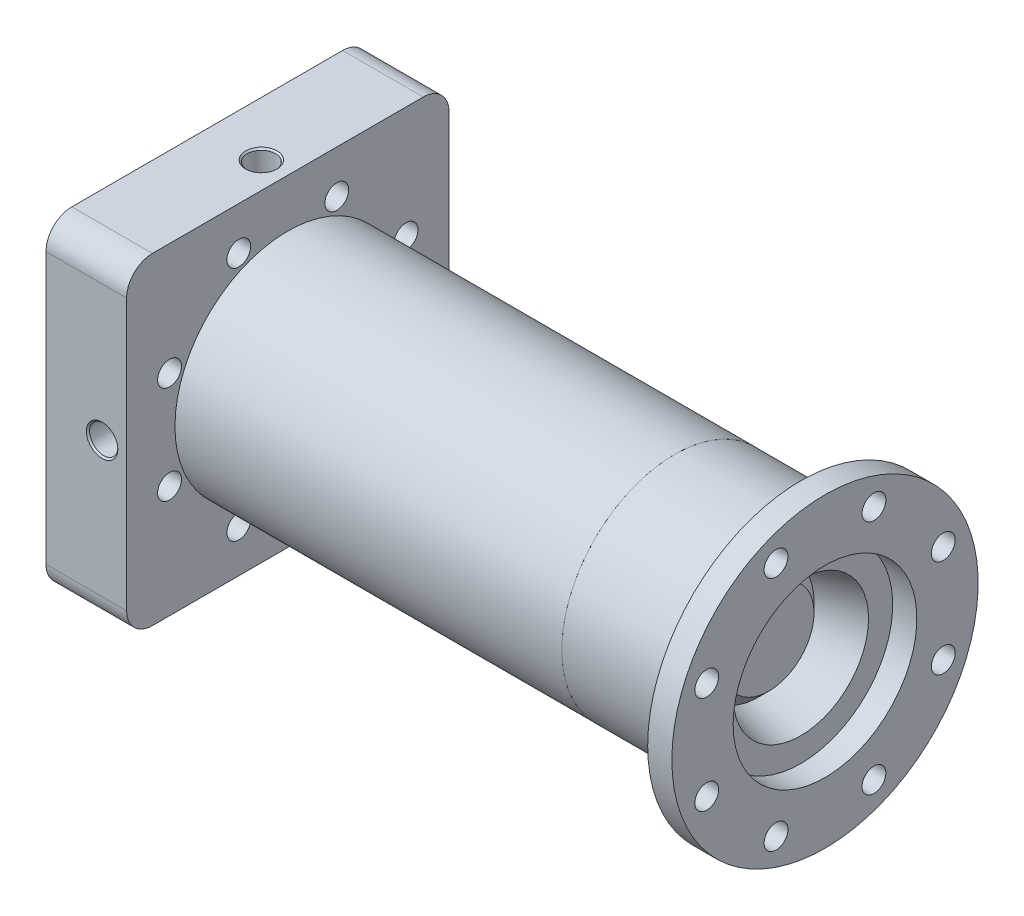
SolidWorks part; units mm, degrees
note: '?' marks a value the reader was unsure of.
other "TC"
other "Injector "
other "Volume "
other "Aft O Ring"
other "Forward O ring" parameters "D11"=9.6936, "D1"=8.9273, "D2"=33.6348, "D3"=26.5468, "D4"=23.315, "D5"=33.6348, "D6"=5.8865, "D7"=63.1196, "D8"=7.0953, "D9"=1.4619, "D10"=3.7307, "D12"=6.1926, "D13"=4.361, "D14"=3.81, "D15"=11.3511, "D16"=3.7343, "D17"=3.7343, "D18"=7.0449
ref_plane "Front Plane" through (0, 0, 0) normal (0, 0, 1) x (1, 0, 0)
ref_plane "Top Plane" through (0, 0, 0) normal (0, 1, 0) x (1, 0, 0)
ref_plane "Right Plane" through (0, 0, 0) normal (1, 0, 0) x (0, 0, -1)
sketch "Chamber Revolve" plane through (0, 0, 0) normal (0, 0, 1) x (1, 0, 0)
  line L1 (227.4697, 63.5) -> (227.4697, 26.67)
  line L4 (189.463, 17.801) -> (173.736, 33.528)
  line L5 (173.736, 33.528) -> (0, 33.528)
  line L10 (0, 33.528) -> (0, 42.164)
  line L11 (0, 63.5) -> (10.16, 63.5)
  line L12 (10.16, 63.5) -> (10.16, 47.244)
  line L13 (0, 0) -> (66.3921, 0) construction
  line L15 (191.9165, 17.1436) -> (227.4697, 26.67)
  line L16 (10.16, 47.244) -> (24.13, 47.244)
  line L17 (24.13, 47.244) -> (24.13, 63.5)
  line L18 (24.13, 63.5) -> (227.4697, 63.5)
  line L19 (190.5, 16.764) -> (191.9165, 17.1436) construction
  line L20 (190.5, 16.764) -> (189.463, 17.801) construction
  line L21 (0, 48.2346) -> (3.8608, 48.2346)
  line L22 (3.8608, 48.2346) -> (3.8608, 42.164)
  line L23 (3.8608, 42.164) -> (0, 42.164)
  line L24 (0, 48.2346) -> (0, 63.5)
  arc A0 (189.463, 17.801) -> (191.9165, 17.1436) centre (191.2591, 19.597) ccw
  dimension "D11" = 2.54
  dimension "D2" = 67.056
  dimension "D3" = 53.34
  dimension "D6" = 45
  dimension "D13" = 10.16
  dimension "D8" = 33.528
  dimension "D9" = 36.9697
  dimension "D7" = 13.716
  dimension "D15" = 13.97
  dimension "D5" = 190.5
  dimension "D4" = 15
  dimension "D18" = 6.0706
  dimension "D12" = 127
revolve "Revolve1" add sketch "Chamber Revolve" angle 360 about L13
fillet "Fillet1" radius 1.27 2 edges at (24.13, 0, 47.244) (10.16, 0, 47.244)
sketch "Sketch2" plane through (0, 0, 0) normal (-1, 0, 0) x (0, 0, 1)
  line L0 (0, 0) -> (-24.3004, 58.6664) construction
  line L1 (0, 0) -> (0, 56.6825) construction
  circle A0 centre (-21.7732, 52.565) radius 3.81
  circle A1 centre (0, 0) radius 63.5 construction
  dimension "D2" = 7.62
  dimension "D1" = 6.604
  dimension "D3" = 22.5
extrude "Cut-Extrude1" cut sketch "Sketch2" against normal up to next
pattern_circular "CirPattern1" count 8 over 360 about axis through (0, 0, 0) along (1, 0, 0) of "Cut-Extrude1"
sketch "Sketch4" plane through (0, 0, 0) normal (-1, 0, 0) x (0, 0, 1)
  circle A0 centre (0, 0) radius 63.5
  circle A1 centre (0, 0) radius 63.5 construction
extrude "Boss-Extrude1" add sketch "Sketch4" along normal blind 31.75 separate body
sketch "Sketch5" plane through (0, 0, 0) normal (1, 0, 0) x (0, 0, -1)
  circle A0 centre (21.7732, 52.565) radius 3.81 construction
  circle A1 centre (21.7732, 52.565) radius 3.81
sketch "Sketch11" plane through (-31.75, 0, 0) normal (-1, 0, 0) x (0, 0, 1)
  line L1 (-63.5, -63.5) -> (63.5, -63.5)
  line L2 (-63.5, -63.5) -> (-63.5, 63.5)
  line L3 (-63.5, 63.5) -> (63.5, 63.5)
  line L4 (63.5, -63.5) -> (63.5, 63.5)
  circle A0 centre (0, 0) radius 63.5 construction
  circle A1 centre (0, 0) radius 63.5
  point P6 (0, 63.5)
  point P9 (-63.5, 0)
  circle M18 centre (0, 0) radius 63.5
  dimension "D1" = 127
extrude "Boss-Extrude2" add sketch "Sketch11" against normal up to surface (31.75 mm away) contours L3 L2 L1 M18 | L1 L4 L3 M18 | L4 L3 M18 | L2 L1 M18
sketch "Sketch12" plane through (0, 0, 0) normal (1, 0, 0) x (0, 0, -1)
  circle A0 centre (0, 0) radius 24.13
  dimension "D1" = 48.26
extrude "Cut-Extrude4" cut sketch "Sketch12" against normal blind 16.51
sketch "Sketch13" plane through (0, 0, 63.5) normal (0, 0, 1) x (1, 0, 0)
  line L1 (0, 63.5) -> (0, -63.5) construction
  line L2 (76.835, 0) -> (-76.835, 0) construction
  circle A0 centre (-9.652, 0) radius 1.9685
  dimension "D1" = 3.937
  dimension "D2" = 9.652
extrude "Cut-Extrude5" cut sketch "Sketch13" against normal up to next and the other way through all
sketch "Sketch14" plane through (0, 0, 0) normal (1, 0, 0) x (0, 0, -1)
  line L0 (-63.5, 63.5) -> (63.5, 63.5) construction
  line L1 (-63.5, -63.5) -> (63.5, -63.5) construction
  line L2 (-12.7, 63.5) -> (-63.5, 63.5)
  line L3 (-63.5, 63.5) -> (-63.5, -63.5)
  line L4 (-63.5, -63.5) -> (-12.7, -63.5)
  arc A0 (-12.7, 63.5) -> (-12.7, -63.5) centre (0, 0) ccw
  circle A1 centre (0, 0) radius 63.5 construction
  dimension "D1" = 12.7
chamfer "Chamfer1" distance 4.572 angle 45 1 edges at (0, 0, -24.13)
sketch "Sketch18" plane through (0, 0, 63.5) normal (0, 0, 1) x (1, 0, 0)
  point P0 (-9.652, 0)
hole_wizard "7/16 (0.4375) Diameter Hole1" positions "Sketch18" profile "Sketch20" hole size "7/16" standard "ANSI Inch"
sketch "Sketch20" plane through (-9.652, 0, 63.5) normal (1, 0, 0) x (0, -1, 0)
  line L0 (0, 0) -> (0, 22.3885)
  line L1 (0, 22.3885) -> (5.5562, 19.05)
  line L2 (5.5562, 19.05) -> (5.5562, 0.635)
  line L3 (5.5562, 0.635) -> (6.1912, 0)
  line L5 (6.1912, 0) -> (0, 0)
  line L6 (-5.5562, 0.635) -> (-6.1912, 0) construction
  line L10 (0, 22.3885) -> (-5.5563, 19.05) construction
  line L11 (0, -6.35) -> (0, 107.95) construction
  dimension "Hole Dia." = 11.1125
  dimension "Hole Depth" = 19.05
  dimension "Near C'Sink Dia." = 12.3825
  dimension "Near C'Sink Angle" = 90
  dimension "Drill Angle" = 118
mirror "Mirror1" about plane through (0, 0, 0) normal (0, 0, 1) of "7/16 (0.4375) Diameter Hole1", "Cut-Extrude5"
sketch "Sketch21" plane through (0, 0, 0) normal (0, 1, 0) x (1, 0, 0)
  line L0 (0, 33.528) -> (173.736, 33.528)
  line L1 (0, 42.164) -> (0, -42.164) construction
  line L2 (0, 33.528) -> (0, -33.528) construction
  line L3 (173.736, -33.528) -> (173.736, 33.528) construction
  line L4 (173.736, 33.528) -> (189.463, 17.801)
  line L5 (189.463, -17.801) -> (189.463, 17.801) construction
  line L6 (189.463, 17.801) -> (189.463, 0)
  line L10 (0, 0) -> (0, 33.528)
  line L11 (0, 0) -> (189.463, 0)
  line L12 (189.463, 0) -> (214.4295, 0) construction
revolve "Revolve2" add sketch "Sketch21" angle 360 about L12
fillet "Fillet2" radius 0.889 2 edges at (3.8608, 0, 42.164) (3.8608, 0, 48.2346)
sketch "Sketch22" plane through (-31.75, 0, 0) normal (-1, 0, 0) x (0, 0, 1)
  point P0 (0, -33.02)
  dimension "D1" = 33.02
hole_wizard "Ø6.7 (6.7) Diameter Hole1" positions "Sketch22" profile "Sketch23" hole size "Ø6.7" standard "ANSI Metric"
sketch "Sketch23" plane through (-31.75, -33.02, 0) normal (0, 1, 0) x (0, 0, 1)
  line L0 (0, 0) -> (0, 15.2209)
  line L1 (0, 15.2209) -> (3.35, 13.208)
  line L2 (3.35, 13.208) -> (3.35, 0.4)
  line L3 (3.35, 0.4) -> (3.75, 0)
  line L5 (3.75, 0) -> (0, 0)
  line L6 (-3.35, 0.4) -> (-3.75, 0) construction
  line L10 (0, 15.2209) -> (-3.35, 13.208) construction
  line L11 (0, -6.35) -> (0, 107.95) construction
  dimension "Hole Dia." = 6.7
  dimension "Hole Depth" = 13.208
  dimension "Near C'Sink Dia." = 7.5
  dimension "Near C'Sink Angle" = 90
  dimension "Drill Angle" = 118
mirror "Mirror2" about plane through (0, 0, 0) normal (0, 1, 0) of "Ø6.7 (6.7) Diameter Hole1"
sketch "Sketch24" plane through (0, 0, 0) normal (0, 1, 0) x (1, 0, 0)
  line L0 (-31.75, 63.5) -> (-31.75, -63.5) construction
  line L1 (-31.75, 7.1374) -> (-30.9581, 5.7658)
  line L2 (-30.9581, 5.7658) -> (-29.845, 5.7658)
  line L3 (-29.4858, 5.617) -> (-28.7329, 4.8641)
  line L4 (-28.7329, 4.8641) -> (-16.51, 4.8641)
  line L5 (-16.51, -24.13) -> (-16.51, 24.13) construction
  line L6 (-16.51, 4.8641) -> (-16.51, 0)
  line L7 (-16.51, 0) -> (-31.75, 0)
  line L8 (-31.75, 0) -> (-31.75, 7.1374)
  line L9 (-29.845, 5.7658) -> (-29.6346, 5.7658) construction
  line L10 (-29.6346, 5.7658) -> (-29.4858, 5.617) construction
  line L11 (-31.75, 0) -> (-56.3457, 0) construction
  arc A0 (-29.845, 5.7658) -> (-29.4858, 5.617) centre (-29.845, 5.2578) cw
  dimension "D2" = 0.508
  dimension "D1" = 60
  dimension "D3" = 4.8641
  dimension "D4" = 7.1374
  dimension "D5" = 5.7658
  dimension "D6" = 1.905
  dimension "D7" = 45
  dimension "D8" = 15.24
ref_axis "Axis1" through (227.4697, 0, 0) along (-1, 0, 0)
revolve "Cut-Revolve1" cut sketch "Sketch24" angle 360 about axis through (227.4697, 0, 0) along (-1, 0, 0)
fillet "Fillet3" radius 0.508 1 edges at (-30.9581, 0, -5.7658)
sketch "Sketch25" plane through (0, 0, 0) normal (0, 0, 1) x (1, 0, 0)
  line L0 (0, -63.5) -> (-31.75, -63.5) construction
  line L1 (0, -63.5) -> (-31.75, -63.5) construction
  line L2 (-4.318, -63.5) -> (-5.4699, -62.8349)
  line L3 (-5.588, -62.6304) -> (-5.588, -61.468)
  line L4 (-11.43, -26.67) -> (-9.398, -26.67)
  line L5 (-5.7368, -61.1088) -> (-6.604, -60.2416)
  line L6 (-6.604, -60.2416) -> (-6.604, -46.8376)
  line L7 (-11.43, -63.5) -> (-11.43, -26.67)
  line L8 (-16.51, -24.13) -> (-16.51, 24.13) construction
  line L9 (-6.604, -46.8376) -> (-9.398, -45.1588)
  line L10 (-9.398, -45.1588) -> (-9.398, -26.67)
  line L11 (-16.51, -24.13) -> (-16.51, 24.13) construction
  line L12 (-11.43, -63.5) -> (-4.318, -63.5)
  line L13 (-11.43, -63.5) -> (-11.43, -73.7659) construction
  arc A1 (-5.588, -61.468) -> (-5.7368, -61.1088) centre (-6.096, -61.468) ccw
  arc A2 (-5.4699, -62.8349) -> (-5.588, -62.6304) centre (-5.3518, -62.6304) cw
  dimension "D4" = 0.2362
  dimension "D6" = 0.508
  dimension "D1" = 7.112
  dimension "D2" = 5.08
  dimension "D3" = 60
  dimension "D5" = 5.842
  dimension "D7" = 45
  dimension "D8" = 2.032
  dimension "D9" = 4.826
  dimension "D10" = 16.6624
  dimension "D11" = 59
  dimension "D12" = 2.032
  dimension "D13" = 2.54
sketch "Sketch29" plane through (0, -63.5, 0) normal (0, -1, 0) x (-1, 0, 0)
  line L0 (0, -63.5) -> (0, 63.5) construction
  point P0 (10.414, 0)
  dimension "D1" = 10.414
hole_wizard "7/16 (0.4375) Diameter Hole2" positions "Sketch29" profile "Sketch30" hole size "7/16" standard "ANSI Inch"
sketch "Sketch30" plane through (-10.414, -63.5, 0) normal (1, 0, 0) x (0, 0, -1)
  line L0 (0, 0) -> (0, 22.3885)
  line L1 (0, 22.3885) -> (5.5562, 19.05)
  line L2 (5.5562, 19.05) -> (5.5562, 0.635)
  line L3 (5.5562, 0.635) -> (6.1913, 0)
  line L5 (6.1913, 0) -> (0, 0)
  line L6 (-5.5562, 0.635) -> (-6.1913, 0) construction
  line L10 (0, 22.3885) -> (-5.5563, 19.05) construction
  line L11 (0, -6.35) -> (0, 107.95) construction
  dimension "Hole Dia." = 11.1125
  dimension "Hole Depth" = 19.05
  dimension "Near C'Sink Dia." = 12.3825
  dimension "Near C'Sink Angle" = 90
  dimension "Drill Angle" = 118
sketch "Sketch31" plane through (0, -63.5, 0) normal (0, -1, 0) x (1, 0, 0)
  circle A0 centre (-10.414, 0) radius 1.5875
  dimension "D1" = 3.175
extrude "Cut-Extrude9" cut sketch "Sketch31" against normal up to surface (39.4223 mm away)
mirror "Mirror3" about plane through (0, 0, 0) normal (0, 1, 0) of "Cut-Extrude9", "7/16 (0.4375) Diameter Hole2"
delete or keep bodies "Body-Delete/Keep 1" type delete bodies bodies 103
sketch "Sketch37" plane through (0, 0, 0) normal (1, 0, 0) x (0, 0, -1)
  line L0 (-63.5, -63.5) -> (63.5, -63.5) construction
  line L1 (-63.5, 63.5) -> (63.5, 63.5) construction
  line L2 (63.5, 63.5) -> (63.5, -63.5) construction
  line L3 (-63.5, 63.5) -> (-63.5, -63.5) construction
  line L4 (-63.5, -63.5) -> (63.5, -63.5)
  line L5 (-63.5, 63.5) -> (63.5, 63.5)
  line L6 (63.5, 63.5) -> (63.5, -63.5)
  line L7 (-63.5, 63.5) -> (-63.5, -63.5)
  circle A0 centre (0, 0) radius 43.688
  dimension "D1" = 87.376
sketch "Sketch32" plane through (0, 0, 0) normal (1, 0, 0) x (0, 0, -1)
  circle A0 centre (0, 0) radius 44.45
  circle A1 centre (0, 0) radius 69.85
  dimension "D1" = 88.9
  dimension "D2" = 139.7
sketch "Sketch33" plane through (0, 0, 0) normal (1, 0, 0) x (0, 0, -1)
  circle A0 centre (0, 0) radius 34.925
  circle A1 centre (0, 0) radius 44.45
  dimension "D1" = 69.85
  dimension "D2" = 88.9
extrude "Boss-Extrude4" add sketch "Sketch33" along normal blind 152.4 separate body
sketch "Sketch34" plane through (0, 0, 0) normal (0, 0, 1) x (1, 0, 0)
  line L2 (152.4, 44.45) -> (152.4, 34.925)
  line L6 (152.4, 34.925) -> (165.1165, 16.764)
  line L7 (165.1165, 16.764) -> (202.0862, 26.67)
  line L8 (202.0862, 26.67) -> (202.0862, 44.45)
  line L9 (202.0862, 44.45) -> (152.4, 44.45)
  line L10 (154.0002, 0) -> (250.6574, 0) construction
  line L11 (152.4, -34.925) -> (152.4, 34.925) construction
  line L12 (152.4, -44.45) -> (152.4, 44.45) construction
  line L13 (152.4, -34.925) -> (152.4, 34.925) construction
  line L14 (152.4, -44.45) -> (152.4, 44.45) construction
  dimension "D1" = 33.528
  dimension "D2" = 53.34
  dimension "D3" = 15
  dimension "D7" = 55
ref_axis "Axis2" through (152.4, 0, 0) along (-1, 0, 0)
revolve "Revolve3" add sketch "Sketch34" angle 360 about axis through (152.4, 0, 0) along (-1, 0, 0)
fillet "Fillet5" radius 1.27 1 edges at (165.1165, 0, -16.764)
sketch "Sketch35" plane through (0, 0, 0) normal (1, 0, 0) x (0, 0, -1)
  line L0 (0, 0) -> (0, 81.6848) construction
  line L1 (0, 0) -> (18.5655, 44.8211) construction
  line L2 (17.0103, 41.0664) -> (18.5655, 44.8211) construction
  circle A0 centre (18.5655, 44.8211) radius 4.064
  circle A1 centre (0, 0) radius 44.45 construction
  dimension "D1" = 8.128
  dimension "D2" = 22.5
  dimension "D3" = 4.064
fillet "Fillet6" radius 10.16 4 edges at (-15.875, -63.5, 63.5) (-15.875, -63.5, -63.5) (-15.875, 63.5, -63.5) (-15.875, 63.5, 63.5)
sketch "Sketch39" plane through (202.0862, 0, 0) normal (1, 0, 0) x (0, 0, -1)
  circle A0 centre (0, 0) radius 36.195
  circle A1 centre (0, 0) radius 60.325
  dimension "D1" = 72.39
  dimension "D2" = 120.65
extrude "Boss-Extrude6" add sketch "Sketch39" along normal blind 9.525 separate body
sketch "Sketch40" plane through (202.0862, 0, 0) normal (-1, 0, 0) x (0, 0, 1)
  line L0 (0, 0) -> (0, 54.3419) construction
  line L1 (0, 0) -> (-19.2945, 46.5811) construction
  circle A0 centre (-19.2945, 46.5811) radius 4.699
  circle A2 centre (0, 0) radius 44.45 construction
  circle A3 centre (0, 0) radius 44.45 construction
  point P5 (-17.0103, 41.0664)
  point P8 (-17.4963, 42.2398)
  dimension "D2" = 9.398
  dimension "D3" = 1.27
  dimension "D1" = 22.5
extrude "Cut-Extrude13" cut sketch "Sketch40" along normal through all both and the other way through all
pattern_circular "CirPattern3" count 8 over 360 about axis through (0, 0, 0) along (1, 0, 0) of "Cut-Extrude13"
sketch "Sketch41" plane through (0, 0, 0) normal (0, 0, 1) x (1, 0, 0)
  line L0 (0, 37.338) -> (-2.1844, 37.338)
  line L1 (0, 53.34) -> (0, -53.34) construction
  line L2 (-2.6416, 37.7952) -> (-2.6416, 40.9702)
  line L3 (-2.1844, 41.4274) -> (0, 41.4274)
  line L4 (0, 0) -> (38.5106, 0) construction
  line L5 (-2.6416, 41.4274) -> (-2.1844, 41.4274) construction
  line L6 (-2.6416, 40.9702) -> (-2.6416, 41.4274) construction
  line L7 (-2.6416, 37.338) -> (-2.6416, 37.7952) construction
  line L8 (-2.1844, 37.338) -> (-2.6416, 37.338) construction
  line L9 (0, 37.338) -> (0, 41.4274)
  arc A0 (-2.1844, 41.4274) -> (-2.6416, 40.9702) centre (-2.1844, 40.9702) ccw
  arc A1 (-2.6416, 37.7952) -> (-2.1844, 37.338) centre (-2.1844, 37.7952) ccw
  dimension "D4" = 0.4572
  dimension "D1" = 4.0894
  dimension "D2" = 2.6416
  dimension "D3" = 41.4274
revolve "Cut-Revolve2" cut sketch "Sketch41" angle 360 about L4
sketch "Sketch43" plane through (0, 0, 0) normal (0, 0, 1) x (1, 0, 0)
  circle A0 centre (-1.1621, 39.5944) radius 1.3347
sketch "Sketch44" plane through (0, 0, 0) normal (0, 0, 1) x (1, 0, 0)
  line L0 (-2.6416, -40.9702) -> (-2.6416, 40.9702) construction
  line L1 (-2.6416, -40.9702) -> (-2.6416, 40.9702) construction
  line L2 (-2.1844, 41.4274) -> (-2.1844, -41.4274) construction
  line L3 (-2.1844, 41.4274) -> (-2.1844, -41.4274) construction
  line L4 (-2.1844, 41.4274) -> (-6.4254, 41.4274) construction
  circle A0 centre (-0.8763, 39.6621) radius 1.7653
  dimension "D1" = 3.5306
revolve "Revolve4" add sketch "Sketch44" angle 360 about L4
ref_plane "Plane1" through (76.2, 0, 0) normal (1, 0, 0) x (0, 0, -1)
sketch "Sketch45" plane through (0, 0, 0) normal (0, 0, 1) x (1, 0, 0)
  line L0 (152.4, 41.4274) -> (154.5336, 41.4274)
  line L1 (152.4, -44.45) -> (152.4, 44.45) construction
  line L2 (155.0416, 40.9194) -> (155.0416, 37.846)
  line L3 (154.5336, 37.338) -> (152.4, 37.338)
  line L4 (152.4, 41.4274) -> (152.4, 37.338)
  line L5 (152.4, 39.3827) -> (151.151, 39.3827) construction
  line L6 (154.5336, 41.4274) -> (155.0416, 41.4274) construction
  line L7 (155.0416, 41.4274) -> (155.0416, 40.9194) construction
  line L8 (155.0416, 37.846) -> (155.0416, 37.338) construction
  line L9 (155.0416, 37.338) -> (154.5336, 37.338) construction
  arc A0 (154.5336, 41.4274) -> (155.0416, 40.9194) centre (154.5336, 40.9194) cw
  arc A1 (154.5336, 37.338) -> (155.0416, 37.846) centre (154.5336, 37.846) ccw
  dimension "D3" = 41.4274
  dimension "D4" = 0.508
  dimension "D1" = 2.6416
  dimension "D2" = 4.0894
revolve "Cut-Revolve3" cut sketch "Sketch45" angle 360 about L4
mirror "Mirror9" about plane through (76.2, 0, 0) normal (1, 0, 0) of bodies 157
ref_axis "Axis3" through (202.0862, 46.5811, -19.2945) along (1, 0, 0)?
equation "\"Throat Diameter\"= 1.32"
equation "\"Exit Diameter\"= 2.1"
equation "\"D3@Chamber Revolve\"=\"Exit Diameter\""
equation "\"D8@Chamber Revolve\"=\"Throat Diameter\""
equation "\"Injector Ox D\"= 3mm"
equation "\"Injector Fuel D\"= 2mm"
equation "\"Chamber Diameter\"= \"Chamber Throat D Ratio\" * ( \"Throat Diameter\" )"
equation "\"Chamber Throat D Ratio\"= 2"
equation "\"L*\"= 30"
equation "\"Lc\"= \"L*\" / ( \"Chamber Throat D Ratio\" ^ 2 )"
equation "\"T_min\"= 2 * .17"
equation "\"D2@Chamber Revolve\"=\"Chamber Diameter\""
equation "\"D7@Chamber Revolve\"=\"T_min\" +.2"
equation "\"D5@Chamber Revolve\"=\"Lc\""
equation "\"No Flange Holes\"= 8"
equation "\"D1@CirPattern1\"=\"No Flange Holes\""
equation "\"D16@Chamber Revolve\"=\"T_min\""
equation "\"D1@Sketch34\"=\"Throat Diameter\""
equation "\"D2@Sketch34\"=\"Exit Diameter\""
equation "\"D3@Sketch35\"=\"D1@Sketch35\"/2"
equation "\"O ring Groove Width\"= .161"
equation "\"Oring Groove Depth\"= .104"
equation "\"O ring Od\"=3.262"
equation "\"D3@Sketch41\"=\"O ring Od\"/2"
equation "\"D1@Sketch41\"=\"O ring Groove Width\""
equation "\"D2@Sketch41\"=\"Oring Groove Depth\""
equation "\"Corner Rad O ring\"= .018"
equation "\"D4@Sketch41\"=\"Corner Rad O ring\""
equation "\"D1@Sketch45\"=\"Oring Groove Depth\""
equation "\"D2@Sketch45\"=\"O ring Groove Width\""
equation "\"D3@Sketch45\"=\"O ring Od\"/2"
